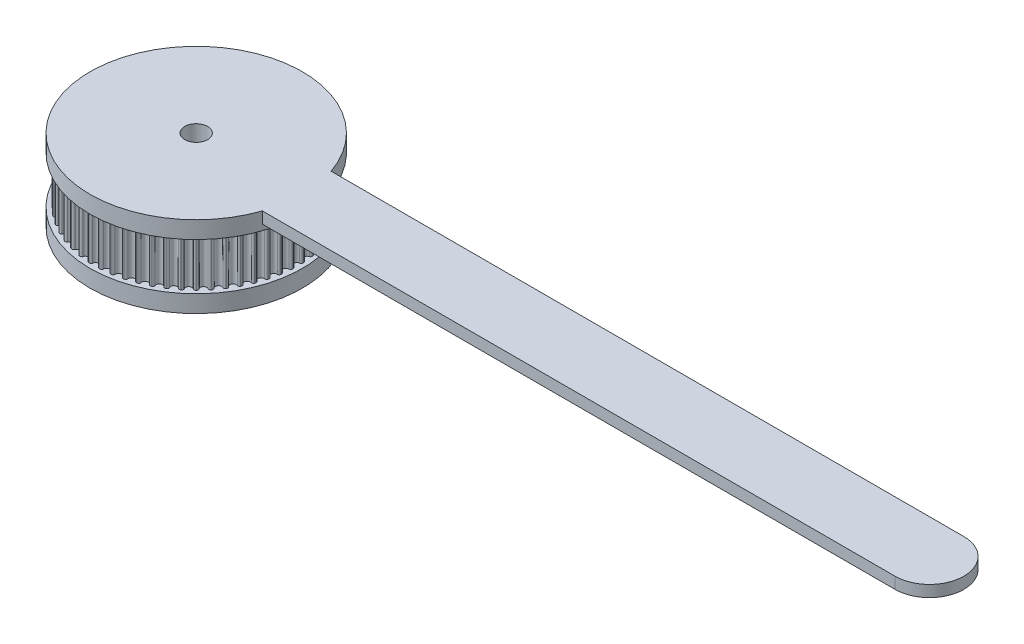
SolidWorks part; units mm, degrees
ref_plane "Front Plane" through (0, 0, 0) normal (0, 0, 1) x (1, 0, 0)
ref_plane "Top Plane" through (0, 0, 0) normal (0, 1, 0) x (1, 0, 0)
ref_plane "Right Plane" through (0, 0, 0) normal (1, 0, 0) x (0, 0, -1)
sketch "Sketch1" plane through (0, 0, 0) normal (0, 1, 0) x (1, 0, 0)
  line L0 (0, 0) -> (0, 28.2667) construction
  line L1 (0, 0) -> (2.9202, 27.7837) construction
  circle A0 centre (0, 0) radius 28.2667 construction
  circle A1 centre (0, 0) radius 27.0467 construction
  circle A2 centre (0, 27.9367) radius 0.89 construction
  circle A5 centre (2.9202, 27.7837) radius 0.89 construction
  arc A6 (0, 27.0467) -> (0.8804, 27.8061) centre (0, 27.9367) ccw
  arc A7 (0.8804, 27.8061) -> (1.3997, 28.2321) centre (1.3749, 27.7327) cw
  arc A8 (1.559, 28.2237) -> (2.031, 27.7458) centre (1.5314, 27.7245) cw
  arc A9 (2.8272, 26.8986) -> (2.031, 27.7458) centre (2.9202, 27.7837) cw
  arc A10 (1.3997, 28.2321) -> (1.559, 28.2237) centre (0, 0) cw
  arc A11 (0, 27.0467) -> (2.8272, 26.8986) centre (0, 0) ccw
  dimension "D1" = 56.5335
  dimension "D3" = 1.78
  dimension "D4" = 0.5
  dimension "D2" = 1.22
  dimension "D5" = 6
extrude "Boss-Extrude1" add sketch "Sketch1" along normal mid plane 13 contours A6 A11 A9 A8 A7 region at (0.001, 0, -0.0192)
ref_axis "Axis1" through (0, 3.3, 0) along (0, -1, 0)
pattern_circular "CirPattern1" count 60 over 360 about axis through (0, 3.3, 0) along (0, -1, 0) of "Boss-Extrude1"
sketch "Sketch2" plane through (0, 0, 0) normal (1, 0, 0) x (0, 0, -1)
  line L10 (0, 6.5) -> (29.4415, 6.5) construction
  line L11 (0, 6.5) -> (0, 8.0875) construction
  line L12 (0, 8.0875) -> (29.4415, 8.0875) construction
  line L15 (29.4415, 6.5) -> (29.4415, 8.0875) construction
  line L20 (0, 3.3) -> (0, -3.3) construction
  line L22 (29.4415, 8.0875) -> (0, 8.0875)
  line L23 (29.4415, 8.0875) -> (29.4415, 6.5)
  line L24 (29.4415, 6.5) -> (0, 6.5)
  line L25 (0, 8.0875) -> (0, 6.5)
  dimension "D1" = 1.5875
  dimension "D2" = 29.4415
  dimension "D3" = 6.5
revolve "Revolve3" add sketch "Sketch2" angle 360 about axis through (0, 3.3, 0) along (0, -1, 0) region at (0, 7.2937, -14.7207)
mirror "Mirror1" about plane through (0, 0, 0) normal (0, 1, 0) of "Revolve3"
sketch "Sketch7" plane through (0, 8.0875, 0) normal (0, 1, 0) x (1, 0, 0)
  line L0 (0, 0) -> (203.2, 0) construction
  line L1 (27.8581, 9.525) -> (203.2, 9.525)
  line L2 (27.8581, -9.525) -> (203.2, -9.525)
  arc A1 (203.2, -9.525) -> (203.2, 9.525) centre (203.2, 0) ccw
  arc A2 (27.8581, 9.525) -> (27.8581, -9.525) centre (0, 0) ccw
  circle A3 centre (0, 0) radius 29.4415 construction
  point P3 (101.6, 0)
  dimension "D1" = 203.2
  dimension "D2" = 19.05
extrude "Boss-Extrude4" add sketch "Sketch7" along normal blind 3.175
sketch "Sketch8" plane through (0, -8.0875, 0) normal (0, -1, 0) x (1, 0, 0)
  circle A0 centre (0, 0) radius 29.4415
  circle A1 centre (0, 0) radius 29.4415 construction
extrude "Boss-Extrude5" add sketch "Sketch8" along normal blind 3.175
sketch "Sketch9" plane through (0, -11.2625, 0) normal (0, -1, 0) x (1, 0, 0)
  circle A0 centre (0, 0) radius 3.175
  dimension "D1" = 6.35
extrude "Cut-Extrude1" cut sketch "Sketch9" against normal through all both and the other way through all
equation "\"TEETH_NUM\"= 60"
equation "\"TOOTH_PITCH\"= 3mm"
equation "\"PITCH_LINE_OFFSET\"= .015in"
equation "\"DIAMETER_PER_GROOVE\"= \"OUTSIDE_DIAMETER\" / \"TEETH_NUM\" * 1in"
equation "\"PITCH_DIAMETER\"= ( ( \"TEETH_NUM\" * 3 - 1.31 ) / 3.1415 + .415 ) * 1mm"
equation "\"OUTSIDE_DIAMETER\"= \"PITCH_DIAMETER\" - \"PITCH_LINE_OFFSET\" * 2"
equation "\"D1@Sketch1\"=\"OUTSIDE_DIAMETER\""
equation "\"TOOTH_HEIGHT\"= 1.22mm"
equation "\"D2@Sketch1\"=\"TOOTH_HEIGHT\""
equation "\"TOOTH_DIAMETER\"= 1.78mm"
equation "\"INTERNAL_RADIUS\"= .5mm"
equation "\"D3@Sketch1\"=\"TOOTH_DIAMETER\""
equation "\"D5@Sketch1\"=360 / \"TEETH_NUM\""
equation "\"D4@Sketch1\"=\"INTERNAL_RADIUS\""
equation "\"D1@CirPattern1\"=\"TEETH_NUM\""
equation "\"BELT_GAP\"= 13mm"
equation "\"D2@Sketch2\"=\"PITCH_DIAMETER\"/2+1/32"
equation "\"D3@Sketch2\"=\"BELT_GAP\"/2"
equation "\"D1@Boss-Extrude1\"=\"BELT_GAP\""
